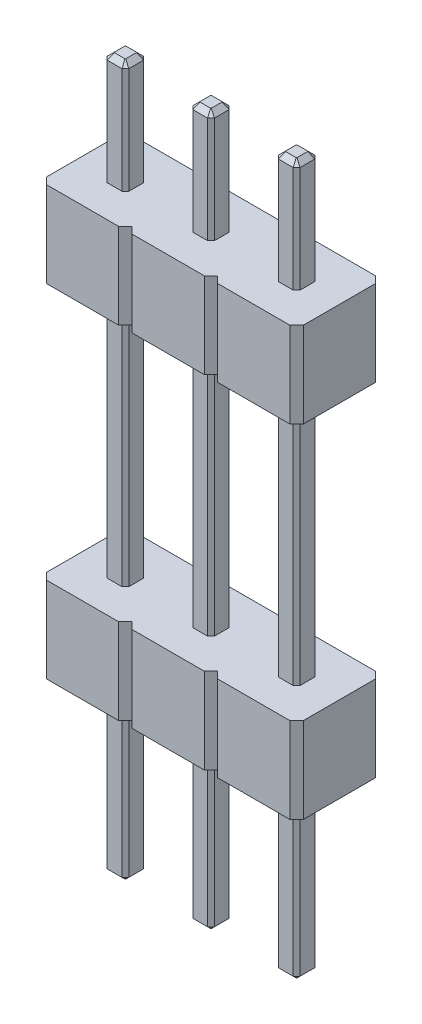
SolidWorks part; units mm, degrees
ref_plane "Спереди" through (0, 0, 0) normal (0, 0, 1) x (1, 0, 0)
ref_plane "Сверху" through (0, 0, 0) normal (0, 1, 0) x (1, 0, 0)
ref_plane "Справа" through (0, 0, 0) normal (1, 0, 0) x (0, 0, -1)
sketch "Эскиз1" plane through (0, 0, 0) normal (0, 1, 0) x (1, 0, 0)
  line L0 (0, 0) -> (0, 5470.6329) construction
  line L1 (0, 0) -> (-5470.6329, 0) construction
  line L2 (-1.59, 0.22) -> (-1.49, 0.32)
  line L3 (-1.49, -0.32) -> (-1.05, -0.32)
  line L4 (-1.59, -0.22) -> (-1.59, 0.22)
  line L5 (-1.49, 0.32) -> (-1.05, 0.32)
  line L6 (-0.95, -0.22) -> (-0.95, 0.22)
  line L7 (-1.59, -0.32) -> (-0.95, 0.32) construction
  line L8 (-1.59, 0.32) -> (-0.95, -0.32) construction
  line L9 (-2.34, 1.27) -> (-0.2, 1.27)
  line L10 (-2.54, 1.07) -> (-2.54, -1.07)
  line L11 (-2.34, -1.27) -> (-0.2, -1.27)
  line L12 (0, 1.07) -> (0, -1.07)
  line L13 (-2.54, 1.27) -> (0, -1.27) construction
  line L14 (-2.54, -1.27) -> (0, 1.27) construction
  line L15 (-1.05, 0.32) -> (-0.95, 0.22)
  line L16 (-1.05, -0.32) -> (-0.95, -0.22)
  line L17 (-1.59, -0.22) -> (-1.49, -0.32)
  line L18 (-2.54, 1.07) -> (-2.34, 1.27)
  line L19 (-0.2, 1.27) -> (0, 1.07)
  line L20 (-0.2, -1.27) -> (0, -1.07)
  line L21 (-2.54, -1.07) -> (-2.34, -1.27)
  line L22 (0.95, 0.22) -> (1.05, 0.32)
  line L23 (1.05, -0.32) -> (1.49, -0.32)
  line L24 (0.95, -0.22) -> (0.95, 0.22)
  line L25 (1.05, 0.32) -> (1.49, 0.32)
  line L26 (1.59, -0.22) -> (1.59, 0.22)
  line L27 (0.2, 1.27) -> (2.34, 1.27)
  line L28 (0, 1.07) -> (0, -1.07)
  line L29 (0.2, -1.27) -> (2.34, -1.27)
  line L30 (2.54, 1.07) -> (2.54, -1.07)
  line L31 (1.49, 0.32) -> (1.59, 0.22)
  line L32 (1.49, -0.32) -> (1.59, -0.22)
  line L33 (0.95, -0.22) -> (1.05, -0.32)
  line L34 (0, 1.07) -> (0.2, 1.27)
  line L35 (2.34, 1.27) -> (2.54, 1.07)
  line L36 (2.34, -1.27) -> (2.54, -1.07)
  line L37 (0, -1.07) -> (0.2, -1.27)
  line L38 (0.95, -0.32) -> (1.59, 0.32) construction
  line L39 (0.95, 0.32) -> (1.59, -0.32) construction
  line L40 (0, 1.27) -> (2.54, -1.27) construction
  line L41 (0, -1.27) -> (2.54, 1.27) construction
  line L42 (3.49, 0.22) -> (3.59, 0.32)
  line L43 (3.59, -0.32) -> (4.03, -0.32)
  line L44 (3.49, -0.22) -> (3.49, 0.22)
  line L45 (3.59, 0.32) -> (4.03, 0.32)
  line L46 (4.13, -0.22) -> (4.13, 0.22)
  line L47 (2.74, 1.27) -> (4.88, 1.27)
  line L48 (2.74, -1.27) -> (4.88, -1.27)
  line L49 (5.08, 1.07) -> (5.08, -1.07)
  line L50 (4.03, 0.32) -> (4.13, 0.22)
  line L51 (4.03, -0.32) -> (4.13, -0.22)
  line L52 (3.49, -0.22) -> (3.59, -0.32)
  line L53 (2.54, 1.07) -> (2.74, 1.27)
  line L54 (4.88, 1.27) -> (5.08, 1.07)
  line L55 (4.88, -1.27) -> (5.08, -1.07)
  line L56 (2.54, -1.07) -> (2.74, -1.27)
  line L57 (3.49, -0.32) -> (4.13, 0.32) construction
  line L58 (3.49, 0.32) -> (4.13, -0.32) construction
  line L59 (2.54, 1.27) -> (5.08, -1.27) construction
  line L60 (2.54, -1.27) -> (5.08, 1.27) construction
  point P5 (-1.27, 0)
  point P10 (-1.27, 0)
  point P31 (3.81, 0)
  point P32 (0, 0)
  point P33 (1.27, 0)
  point P38 (1.27, 0)
  point P63 (3.81, 0)
  point P84 (0, 0)
  dimension "D1" = 0.64
  dimension "D2" = 1.27
  dimension "D3" = 2
  dimension "D4" = 2
extrude "Бобышка-Вытянуть1" add sketch "Эскиз1" against normal blind 5.08 contours L4 L17 L3 L16 L6 L15 L5 L2 | L24 L33 L23 L32 L26 L31 L25 L22 | L44 L52 L43 L51 L46 L50 L45 L42 region at (-1.27, 0, 0) region at (1.27, 0, 0) region at (3.81, 0, 0)
extrude "Бобышка-Вытянуть2" add sketch "Эскиз1<3>" along normal blind 16 contours L4 L17 L3 L16 L6 L15 L5 L2 | L24 L33 L23 L32 L26 L31 L25 L22 | L44 L52 L43 L51 L46 L50 L45 L42 region at (-1.27, 0, 0) region at (1.27, 0, 0) region at (3.81, 0, 0)
sketch "Эскиз1<3>" plane through (0, 0, 0) normal (0, 1, 0) x (1, 0, 0) same geometry as "Эскиз1"
extrude "Бобышка-Вытянуть3" add sketch "Эскиз1<4>" along normal blind 2.54 contours L10 L21 L11 L20 L12 L19 L9 L18 L17 L4 L2 L5 L15 L6 L16 L3 | L12 L37 L29 L36 L30 L35 L27 L34 L33 L24 L22 L25 L31 L26 L32 L23 | L30 L56 L48 L55 L49 L54 L47 L53 L52 L44 L42 L45 L50 L46 L51 L43 region at (-1.27, 0, -1.2341) region at (0.1254, 0, -1.1446) region at (2.6654, 0, -1.1446)
sketch "Эскиз1<4>" plane through (0, 0, 0) normal (0, 1, 0) x (1, 0, 0) same geometry as "Эскиз1"
extrude "Бобышка-Вытянуть4" add sketch "Эскиз1<5>" against normal blind 2.54 from offset 12.7 contours L10 L21 L11 L20 L12 L19 L9 L18 L17 L4 L2 L5 L15 L6 L16 L3 | L12 L37 L29 L36 L30 L35 L27 L34 L33 L24 L22 L25 L31 L26 L32 L23 | L30 L56 L48 L55 L49 L54 L47 L53 L52 L44 L42 L45 L50 L46 L51 L43 region at (-1.27, 0, -1.2341) region at (0.1254, 0, -1.1446) region at (2.6654, 0, -1.1446)
sketch "Эскиз1<5>" plane through (0, 0, 0) normal (0, 1, 0) x (1, 0, 0) same geometry as "Эскиз1"
chamfer "Фаска1" distance 0.15 angle 45 48 edges at (-1.54, -5.08, 0.27) (-1.27, -5.08, 0.32) (-1, -5.08, 0.27) (-0.95, -5.08, 0) (-1, -5.08, -0.27) (-1.27, -5.08, -0.32) (-1.54, -5.08, -0.27) (-1.59, -5.08, 0) (1, -5.08, 0.27) (1.27, -5.08, 0.32) (1.54, -5.08, 0.27) (1.59, -5.08, 0) (1.54, -5.08, -0.27) (1.27, -5.08, -0.32) (1, -5.08, -0.27) (0.95, -5.08, 0) (1, 16, -0.27) (1.27, 16, -0.32) (1.54, 16, -0.27) (1.59, 16, 0) (1.54, 16, 0.27) (1.27, 16, 0.32) (1, 16, 0.27) (0.95, 16, 0) (-1.54, 16, -0.27) (-1.27, 16, -0.32) (-1, 16, -0.27) (-0.95, 16, 0) (-1, 16, 0.27) (-1.27, 16, 0.32) (-1.54, 16, 0.27) (-1.59, 16, 0) (3.54, 16, -0.27) (3.81, 16, -0.32) (4.08, 16, -0.27) (4.13, 16, 0) (4.08, 16, 0.27) (3.81, 16, 0.32) (3.54, 16, 0.27) (3.49, 16, 0) (3.54, -5.08, 0.27) (3.81, -5.08, 0.32) (4.08, -5.08, 0.27) (4.13, -5.08, 0) (4.08, -5.08, -0.27) (3.81, -5.08, -0.32) (3.54, -5.08, -0.27) (3.49, -5.08, 0)
